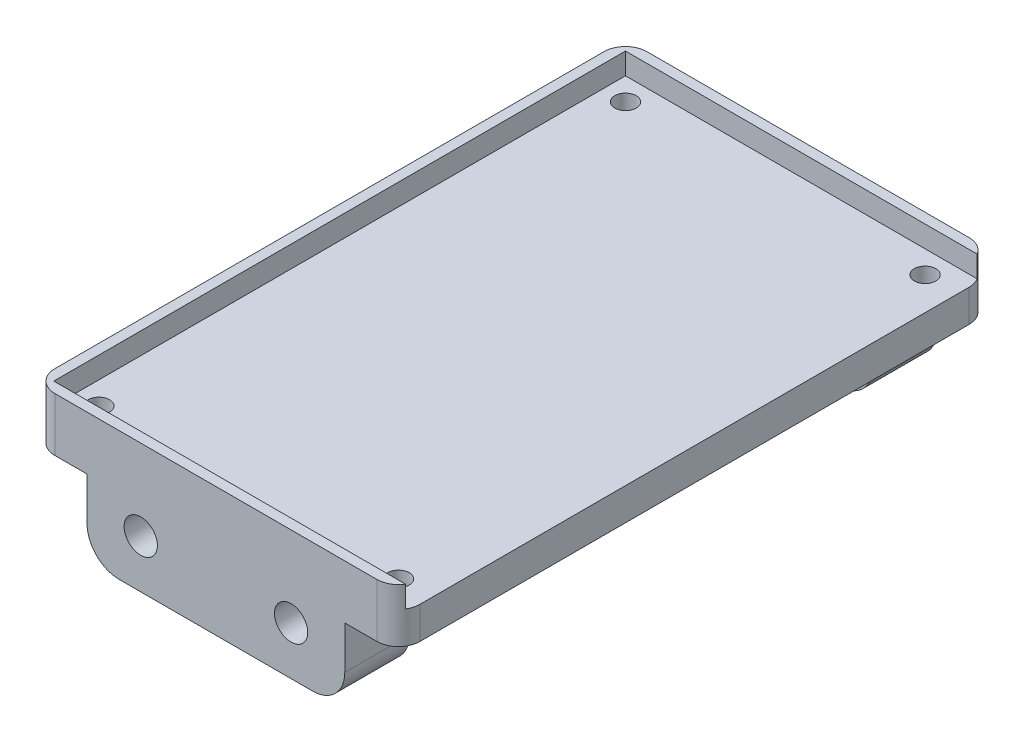
SolidWorks part; units mm, degrees
ref_plane "前视基准面" through (0, 0, 0) normal (0, 0, 1) x (1, 0, 0)
ref_plane "上视基准面" through (0, 0, 0) normal (0, 1, 0) x (1, 0, 0)
ref_plane "右视基准面" through (0, 0, 0) normal (1, 0, 0) x (0, 0, -1)
other "Configuration Table"
sketch "草图1" plane through (0, 0, 0) normal (0, 1, 0) x (1, 0, 0)
  line L1 (0, 0) -> (34, 0)
  line L2 (0, 0) -> (0, 55.14)
  line L3 (0, 55.14) -> (34, 55.14)
  line L4 (34, 0) -> (34, 55.14)
  dimension "D1" = 34
  dimension "D2" = 55.14
extrude "凸台-拉伸1" add sketch "草图1" along normal blind 5
sketch "草图2" plane through (0, 5, 0) normal (0, 1, 0) x (1, 0, 0)
  line L0 (0.95, 54.19) -> (33.05, 54.19)
  line L2 (0, 55.14) -> (0, 0)
  line L3 (0, 0) -> (34, 0)
  line L4 (34, 55.14) -> (34, 0)
  line L5 (33.05, 54.19) -> (33.05, 0.95)
  line L6 (0.95, 0.95) -> (33.05, 0.95)
  line L7 (0.95, 54.19) -> (0.95, 0.95)
  line L8 (0, 55.14) -> (34, 55.14) construction
  dimension "D1" = 0.95
extrude "切除-拉伸1" cut sketch "草图2" against normal blind 2 contours L0 L7 L6 L5 region at (17, 5, -27.57)
sketch "草图3" plane through (34, 0, 0) normal (1, 0, 0) x (0, 0, -1)
  line L0 (0, 5) -> (55.14, 5) construction
  line L1 (52.57, 10) -> (2.57, 10)
  line L2 (52.57, 10) -> (52.57, 0)
  line L3 (52.57, 0) -> (2.57, 0)
  line L4 (2.57, 10) -> (2.57, 0)
  line L5 (52.57, 10) -> (2.57, 0) construction
  line L6 (52.57, 0) -> (2.57, 10) construction
  line L7 (0, 0) -> (55.14, 0) construction
  point P0 (27.57, 5)
  dimension "D1" = 50
extrude "切除-拉伸2" cut sketch "草图3" against normal blind 2
fillet "圆角3" radius 2 1 edges at (0, 2.5, 0) type face fillet first side face at (17, 2.5, 0) second side face at (0, 2.5, -27.57)
fillet "圆角4" radius 2 1 edges at (0, 2.5, -55.14) type face fillet first side face at (0, 2.5, -28.57) second side face at (17, 2.5, -55.14)
fillet "圆角5" radius 2 1 edges at (34, 2.5, -55.14) type face fillet first side face at (18, 2.5, -55.14) second side face at (34, 2.5, -53.855)
fillet "圆角6" radius 2 1 edges at (34, 2.5, 0) type face fillet first side face at (18, 2.5, 0) second side face at (34, 2.5, -1.285)
sketch "草图5" plane through (0, 3, 0) normal (0, 1, 0) x (1, 0, 0)
  line L0 (17, -945.81) -> (17, 49054.19) construction
  line L1 (0.95, 54.19) -> (3.05, 54.19)
  line L2 (0.95, 54.19) -> (0.95, 52.09)
  line L3 (0.95, 52.09) -> (3.05, 52.09)
  line L4 (3.05, 54.19) -> (3.05, 52.09)
  line L6 (-999.05, 27.57) -> (49000.95, 27.57) construction
  line L7 (0.95, 54.19) -> (0.95, 0.95) construction
  line L8 (0.95, 54.19) -> (33.05, 54.19) construction
  circle A0 centre (3.05, 52.09) radius 1
  circle A1 centre (3.05, 3.05) radius 1
  circle A2 centre (30.95, 3.05) radius 1
  circle A3 centre (30.95, 52.09) radius 1
  point P13 (0.95, 27.57)
  point P16 (17, 54.19)
  dimension "D3" = 2
  dimension "D1" = 2.1
  dimension "D2" = 2.1
extrude "切除-拉伸3" cut sketch "草图5" against normal blind 5 contours A2 | A3 | A0 | A1
sketch "草图6" plane through (0, 3, 0) normal (0, 1, 0) x (1, 0, 0)
  line L0 (5.05, 49.09) -> (5.05, 6.05)
  line L1 (3.05, 52.09) -> (30.95, 52.09)
  line L2 (3.05, 52.09) -> (3.05, 3.05)
  line L3 (3.05, 3.05) -> (30.95, 3.05)
  line L4 (30.95, 52.09) -> (30.95, 3.05)
  line L5 (6.05, 5.05) -> (6.2547, 5.05)
  line L6 (28.95, 50.09) -> (28.95, 5.05)
  line L7 (6.05, 50.09) -> (6.2547, 50.09)
  line L8 (10.05, 49.09) -> (10.05, 6.05)
  line L13 (5.05, 50.09) -> (7.2547, 50.09)
  line L14 (5.05, 50.09) -> (5.05, 5.05)
  line L15 (5.05, 5.05) -> (7.2547, 5.05)
  line L16 (7.2547, 49.09) -> (7.2547, 6.05)
  line L17 (11.05, 50.09) -> (11.2547, 50.09)
  line L18 (12.2547, 49.09) -> (12.2547, 6.05)
  line L19 (11.05, 5.05) -> (11.2547, 5.05)
  line L20 (15.05, 49.09) -> (15.05, 6.05)
  line L21 (16.05, 50.09) -> (16.2547, 50.09)
  line L22 (17.2547, 49.09) -> (17.2547, 6.05)
  line L23 (16.05, 5.05) -> (16.2547, 5.05)
  line L24 (20.05, 49.09) -> (20.05, 6.05)
  line L25 (21.05, 50.09) -> (21.2547, 50.09)
  line L26 (22.2547, 49.09) -> (22.2547, 6.05)
  line L27 (21.05, 5.05) -> (21.2547, 5.05)
  line L28 (25.05, 49.09) -> (25.05, 6.05)
  line L29 (26.05, 50.09) -> (26.2547, 50.09)
  line L30 (27.2547, 49.09) -> (27.2547, 6.05)
  line L31 (26.05, 5.05) -> (26.2547, 5.05)
  line L32 (5.05, 50.09) -> (28.95, 50.09) construction
  line L33 (5.05, 5.05) -> (28.95, 5.05) construction
  line L34 (5.05, 50.09) -> (5.05, 5.05) construction
  arc A0 (6.2547, 50.09) -> (7.2547, 49.09) centre (6.2547, 49.09) cw
  arc A1 (6.2547, 5.05) -> (7.2547, 6.05) centre (6.2547, 6.05) ccw
  arc A2 (6.05, 5.05) -> (5.05, 6.05) centre (6.05, 6.05) cw
  arc A3 (5.05, 49.09) -> (6.05, 50.09) centre (6.05, 49.09) cw
  arc A4 (26.2547, 50.09) -> (27.2547, 49.09) centre (26.2547, 49.09) cw
  arc A5 (25.05, 49.09) -> (26.05, 50.09) centre (26.05, 49.09) cw
  arc A6 (26.2547, 5.05) -> (27.2547, 6.05) centre (26.2547, 6.05) ccw
  arc A7 (26.05, 5.05) -> (25.05, 6.05) centre (26.05, 6.05) cw
  arc A8 (21.2547, 5.05) -> (22.2547, 6.05) centre (21.2547, 6.05) ccw
  arc A9 (20.05, 6.05) -> (21.05, 5.05) centre (21.05, 6.05) ccw
  arc A10 (21.2547, 50.09) -> (22.2547, 49.09) centre (21.2547, 49.09) cw
  arc A11 (20.05, 49.09) -> (21.05, 50.09) centre (21.05, 49.09) cw
  arc A12 (16.2547, 50.09) -> (17.2547, 49.09) centre (16.2547, 49.09) cw
  arc A13 (15.05, 49.09) -> (16.05, 50.09) centre (16.05, 49.09) cw
  arc A14 (16.2547, 5.05) -> (17.2547, 6.05) centre (16.2547, 6.05) ccw
  arc A15 (16.05, 5.05) -> (15.05, 6.05) centre (16.05, 6.05) cw
  arc A16 (11.2547, 5.05) -> (12.2547, 6.05) centre (11.2547, 6.05) ccw
  arc A17 (10.05, 6.05) -> (11.05, 5.05) centre (11.05, 6.05) ccw
  arc A18 (11.2547, 50.09) -> (12.2547, 49.09) centre (11.2547, 49.09) cw
  arc A19 (10.05, 49.09) -> (11.05, 50.09) centre (11.05, 49.09) cw
  dimension "D3" = 1
  dimension "D4" = 1
  dimension "D1" = 2
  dimension "D2" = 5
extrude "切除-拉伸5" cut sketch "草图6" against normal blind 5 contours A3 L0 A2 L5 A1 L16 A0 L7 | A19 L8 A17 L19 A16 L18 A18 L17 | A11 L24 A9 L27 A8 L26 A10 L25 | A7 L31 A6 L30 A4 L29 A5 L28 | L20 A15 L23 A14 L22 A12 L21 A13 region at (6.1524, 3, -27.57) region at (11.1524, 3, -27.57) region at (21.1524, 3, -27.57) region at (26.1524, 3, -27.57)
sketch "草图7" plane through (0, 0, 0) normal (0, -1, 0) x (1, 0, 0)
  line L1 (3.3369, -4.5252) -> (27.9146, -4.5252)
  line L2 (3.3369, -4.5252) -> (3.3369, -50.6148)
  line L3 (3.3369, -50.6148) -> (27.9146, -50.6148)
  line L4 (27.9146, -4.5252) -> (27.9146, -50.6148)
extrude "凸台-拉伸3" add sketch "草图7" against normal blind 3
sketch "草图8" plane through (0, 0, 0) normal (0, -1, 0) x (1, 0, 0)
  line L0 (17, 0) -> (17, -3)
  line L1 (2, 0) -> (32, 0) construction
  line L3 (7, -6) -> (27, -6)
  line L4 (7, -6) -> (7, 0)
  line L5 (7, 0) -> (27, 0)
  line L6 (27, -6) -> (27, 0)
  line L7 (7, -6) -> (27, 0) construction
  line L8 (7, 0) -> (27, -6) construction
  line M7 (32, 0) -> (2, 0)
  dimension "D1" = 3
  dimension "D2" = 6
  dimension "D3" = 20
extrude "凸台-拉伸5" add sketch "草图8" along normal blind 5 contours L3 L6 L4 M7 region at (7.2088, 0, -3)
sketch "草图9" plane through (0, 0, 0) normal (0, -1, 0) x (1, 0, 0)
  line L0 (17, -55.14) -> (17, -52.14)
  line L1 (32, -55.14) -> (2, -55.14) construction
  line L3 (7, -55.14) -> (27, -55.14)
  line L4 (7, -55.14) -> (7, -49.14)
  line L5 (7, -49.14) -> (27, -49.14)
  line L6 (27, -55.14) -> (27, -49.14)
  line L7 (7, -55.14) -> (27, -49.14) construction
  line L8 (7, -49.14) -> (27, -55.14) construction
  line M14 (2, -55.14) -> (32, -55.14)
  dimension "D1" = 3
  dimension "D2" = 6
  dimension "D3" = 20
extrude "凸台-拉伸6" add sketch "草图9" along normal blind 5 contours L6 L5 L4 M14 region at (7.2088, 0, -52.14)
sketch "草图10" plane through (0, 0, -55.14) normal (0, 0, -1) x (-1, 0, 0)
  line L1 (-27, -5) -> (-24, -5)
  line L2 (-27, -5) -> (-27, -2.5)
  line L3 (-27, -2.5) -> (-24, -2.5)
  line L4 (-24, -5) -> (-24, -2.5)
  line L5 (-7, -5) -> (-10, -5)
  line L6 (-7, -5) -> (-7, -2.5)
  line L7 (-7, -2.5) -> (-10, -2.5)
  line L8 (-10, -5) -> (-10, -2.5)
  circle A0 centre (-24, -2.5) radius 2
  circle A1 centre (-10, -2.5) radius 2
  dimension "D3" = 4
  dimension "D6" = 4
  dimension "D1" = 2.5
  dimension "D2" = 3
  dimension "D4" = 2.5
  dimension "D5" = 3
extrude "切除-拉伸6" cut sketch "草图10" against normal through all contours L7 A1 L8 | L8 A1 L7 | L3 A0 L4 | L4 A0 L3 region at (24.8488, -3.3488, -55.14) region at (23.7171, -2.2171, -55.14) region at (10.2829, -2.2171, -55.14) region at (9.1512, -3.3488, -55.14)
sketch "草图11" plane through (0, 0, 0) normal (0, -1, 0) x (1, 0, 0)
  line L1 (32, -2.57) -> (34, -2.57)
  line L2 (32, -2.57) -> (32, -52.57)
  line L3 (32, -52.57) -> (34, -52.57)
  line L4 (34, -2.57) -> (34, -52.57)
extrude "凸台-拉伸7" add sketch "草图11" against normal blind 3
sketch "草图12" plane through (0, 0, -55.14) normal (0, 0, -1) x (-1, 0, 0)
  line L0 (-17, -995) -> (-17, 49005) construction
  line L1 (-27, 0) -> (-29, 0)
  line L2 (-27, 0) -> (-27, -5)
  line L3 (-27, -5) -> (-29, -5)
  line L4 (-29, 0) -> (-29, -5)
  line L5 (-32, 5) -> (-2, 5) construction
  line L6 (-7, -5) -> (-5, -5)
  line L7 (-7, 0) -> (-7, -5)
  line L8 (-7, 0) -> (-5, 0)
  line L9 (-5, 0) -> (-5, -5)
  point P10 (-17, 5)
  dimension "D1" = 2
extrude "凸台-拉伸8" add sketch "草图12" against normal blind 6
sketch "草图13" plane through (0, 0, 0) normal (0, 0, 1) x (1, 0, 0)
  line L1 (7, 0) -> (5, 0)
  line L2 (7, 0) -> (7, -5)
  line L3 (7, -5) -> (5, -5)
  line L4 (5, 0) -> (5, -5)
  line L5 (27, 0) -> (29, 0)
  line L6 (27, 0) -> (27, -5)
  line L7 (27, -5) -> (29, -5)
  line L8 (29, 0) -> (29, -5)
extrude "凸台-拉伸9" add sketch "草图13" against normal blind 6
sketch "草图14" plane through (0, -5, 0) normal (0, -1, 0) x (1, 0, 0)
  line L1 (5, 0) -> (29, 0)
  line L2 (5, 0) -> (5, -6)
  line L3 (5, -6) -> (29, -6)
  line L4 (29, 0) -> (29, -6)
  line L5 (5, -55.14) -> (29, -55.14)
  line L6 (5, -55.14) -> (5, -49.14)
  line L7 (5, -49.14) -> (29, -49.14)
  line L8 (29, -55.14) -> (29, -49.14)
extrude "凸台-拉伸10" add sketch "草图14" along normal blind 2
sketch "草图15" plane through (0, 0, -55.14) normal (0, 0, -1) x (-1, 0, 0)
  circle A0 centre (-24, -2.5) radius 2
  circle A1 centre (-24, -2.5) radius 1.55
  dimension "D1" = 3.1
extrude "凸台-拉伸11" add sketch "草图15" against normal blind 6
sketch "草图16" plane through (0, 0, -55.14) normal (0, 0, -1) x (-1, 0, 0)
  circle A0 centre (-10, -2.5) radius 2
  circle A1 centre (-10, -2.5) radius 1.55
  dimension "D1" = 3.1
extrude "凸台-拉伸12" add sketch "草图16" against normal blind 6
sketch "草图17" plane through (0, 0, 0) normal (0, 0, 1) x (1, 0, 0)
  circle A0 centre (10, -2.5) radius 2
  circle A1 centre (24, -2.5) radius 2
  circle A2 centre (10, -2.5) radius 1.55
  circle A3 centre (24, -2.5) radius 1.55
extrude "凸台-拉伸13" add sketch "草图17" against normal blind 6
fillet "圆角7" radius 3 1 edges at (5, -7, -52.14) type face fillet first side face at (17, -7, -52.14) second side face at (5, -3.5, -52.14)
fillet "圆角8" radius 3 1 edges at (29, -7, -52.14) type face fillet first side face at (18.5, -7, -52.14) second side face at (29, -3.5, -52.14)
fillet "圆角9" radius 3 1 edges at (29, -7, -3) type face fillet first side face at (17, -7, -3) second side face at (29, -3.5, -3)
fillet "圆角10" radius 3 1 edges at (5, -7, -3) type face fillet first side face at (15.5, -7, -3) second side face at (5, -3.5, -3)
sketch "草图18" plane through (0, 3, 0) normal (0, 1, 0) x (1, 0, 0)
  line L1 (33.05, 54.19) -> (34.6713, 54.19)
  line L2 (33.05, 54.19) -> (33.05, 0.95)
  line L3 (33.05, 0.95) -> (34.6713, 0.95)
  line L4 (34.6713, 54.19) -> (34.6713, 0.95)
extrude "切除-拉伸7" cut sketch "草图18" along normal blind 2
